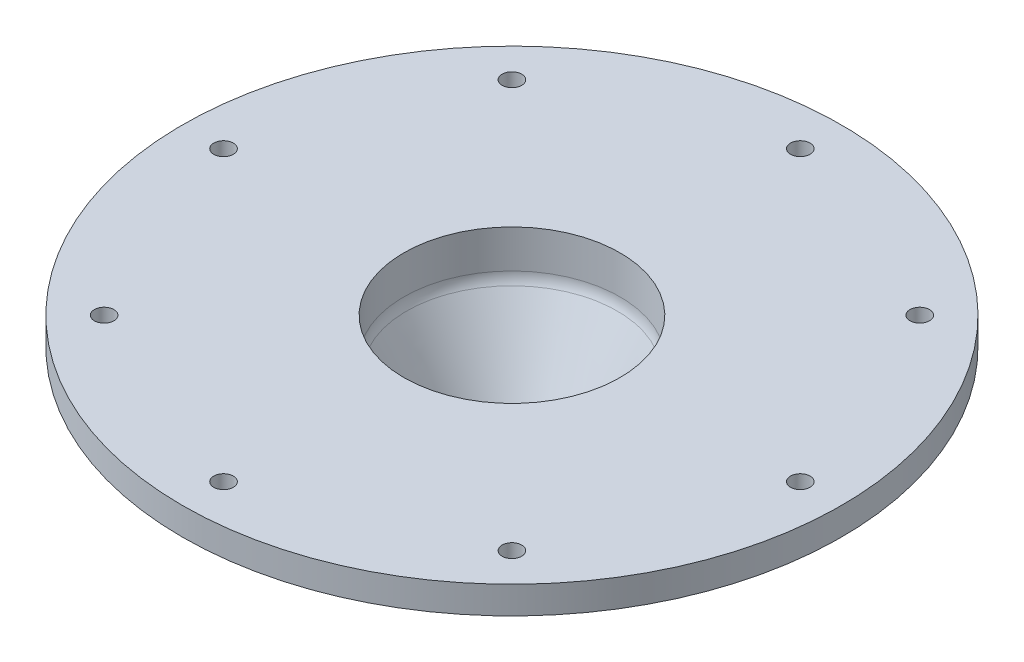
SolidWorks part; units mm, degrees
material "7075-T6 (SN)"
ref_plane "Front Plane" through (0, 0, 0) normal (0, 0, 1) x (1, 0, 0)
ref_plane "Top Plane" through (0, 0, 0) normal (0, 1, 0) x (1, 0, 0)
ref_plane "Right Plane" through (0, 0, 0) normal (1, 0, 0) x (0, 0, -1)
sketch "Sketch1" plane through (0, 0, 0) normal (0, 1, 0) x (1, 0, 0)
  circle A0 centre (0, 0) radius 38.1
  dimension "D1" = 76.2
extrude "Boss-Extrude1" add sketch "Sketch1" along normal blind 3.175
hole_wizard "Tap Drill for #4-40 Tap1" positions "Sketch3" profile "Sketch4" hole size "#4-40" standard "ANSI Inch" end condition through all
sketch "Sketch3" plane through (0, 0, 0) normal (0, -1, 0) x (-1, 0, 0)
  point P0 (0, -33.3375)
  dimension "D1" = 33.3375
sketch "Sketch4" plane through (0, 0, 33.3375) normal (1, 0, 0) x (0, 0, -1)
  line L0 (0, 0) -> (0, 3.175)
  line L1 (0, 3.175) -> (1.1303, 3.175)
  line L2 (1.1303, 3.175) -> (1.1303, 0)
  line L5 (1.1303, 0) -> (0, 0)
  line L11 (0, -6.35) -> (0, 107.95) construction
  dimension "Thru Hole Dia." = 2.2606
  dimension "Thru Hole Depth" = 3.175
pattern_circular "CirPattern1" count 8 over 360 about axis through (0, 0, 0) along (0, 1, 0) of "Tap Drill for #4-40 Tap1"
sketch "Sketch5" plane through (0, 0, 0) normal (0, -1, 0) x (1, 0, 0)
  circle A0 centre (0, 0) radius 25.4
  dimension "D1" = 50.8
extrude "Boss-Extrude2" add sketch "Sketch5" along normal blind 19.05
sketch "Sketch6" plane through (0, -19.05, 0) normal (0, -1, 0) x (1, 0, 0)
  circle A0 centre (0, 0) radius 4.7625
  dimension "D1" = 9.525
extrude "Cut-Extrude1" cut sketch "Sketch6" against normal through all both and the other way through all
sketch "Sketch7" plane through (0, 3.175, 0) normal (0, 1, 0) x (1, 0, 0)
  circle A0 centre (0, 0) radius 12.5
  dimension "D1" = 25
extrude "Cut-Extrude2" cut sketch "Sketch7" against normal blind 5.08
sketch "Sketch8" plane through (0, -1.905, 0) normal (0, 1, 0) x (1, 0, 0)
  circle A0 centre (0, 0) radius 12.5
  circle A1 centre (0, 0) radius 12.5 construction
  dimension "D1" = 0
ref_plane "Plane1" through (0, -15.875, 0) normal (0, -1, 0) x (-1, 0, 0)
sketch "Sketch9" plane through (0, -15.875, 0) normal (0, -1, 0) x (-1, 0, 0)
  circle A0 centre (0, 0) radius 4.7625
  circle A1 centre (0, 0) radius 4.7625 construction
  dimension "D1" = 0
loft "Cut-Loft1" cut profiles "Sketch8", "Sketch9" connector at (0, -1.905, 12.5) connector at (-1.301, -15.875, 4.5814)
chamfer "Chamfer1" distance 16.51 angle 45 1 edges at (0, -19.05, -25.4)
fillet "Fillet1" radius 2.54 1 edges at (0, 0, 25.4)
fillet "Fillet2" radius 2.54 1 edges at (0, -1.905, 12.5)
